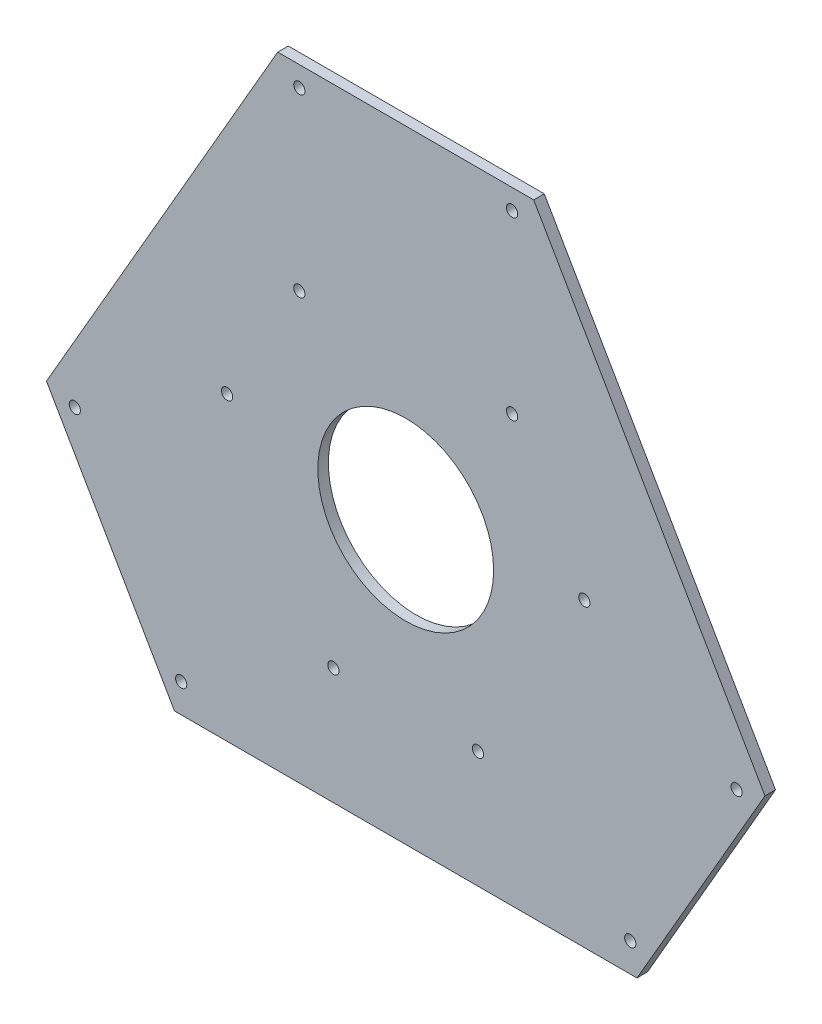
SolidWorks part; units mm, degrees
ref_plane "正面" through (0, 0, 0) normal (0, 0, 1) x (1, 0, 0)
ref_plane "平面" through (0, 0, 0) normal (0, 1, 0) x (1, 0, 0)
ref_plane "右側面" through (0, 0, 0) normal (1, 0, 0) x (0, 0, -1)
sketch "ｽｹｯﾁ1" plane through (0, 0, 0) normal (0, 0, 1) x (1, 0, 0)
  line L0 (0, -55) -> (0, 55) construction
  line L30 (-36.3988, 96.9554) -> (36.3988, 96.9554)
  line L31 (0, 160) -> (-138.5641, -80) construction
  line L32 (-138.5641, -80) -> (138.5641, -80) construction
  line L33 (138.5641, -80) -> (0, 160) construction
  line L34 (36.3988, 96.9554) -> (102.1653, -16.9554)
  line L35 (102.1653, -16.9554) -> (65.7665, -80)
  line L36 (65.7665, -80) -> (-65.7665, -80)
  line L37 (-65.7665, -80) -> (-102.1653, -16.9554)
  line L38 (-102.1653, -16.9554) -> (-36.3988, 96.9554)
  circle A0 centre (30.25, 91.1955) radius 1.6
  circle A1 centre (30.25, 41.1955) radius 1.6
  circle A2 centre (-30.25, 41.1955) radius 1.6
  circle A3 centre (-30.25, 91.1955) radius 1.6
  circle A4 centre (63.8526, -71.795) radius 1.6
  circle A5 centre (94.1026, -19.4005) radius 1.6
  circle A6 centre (50.8013, 5.5995) radius 1.6
  circle A7 centre (20.5513, -46.795) radius 1.6
  circle A8 centre (-94.1026, -19.4005) radius 1.6
  circle A9 centre (-63.8526, -71.795) radius 1.6
  circle A10 centre (-20.5513, -46.795) radius 1.6
  circle A11 centre (-50.8013, 5.5995) radius 1.6
  circle A12 centre (0, 0) radius 80 construction
  circle A17 centre (0, 0) radius 25
  point P0 (0, 60)
  point P1 (0, 0)
  point P2 (0, 0)
  point P46 (0, 0)
  point P48 (0, -80)
  point P76 (0, 0)
  dimension "D1" = 3.2
  dimension "D17" = 50
  dimension "D4" = 50
  dimension "D9" = 80
  dimension "D7" = 3
extrude "ﾎﾞｽ - 押し出し1" add sketch "ｽｹｯﾁ1" along normal blind 3 contours L38 L37 L36 L35 L34 L30 A11 A9 A8 A7 A5 A4 A2 A1 A0 region at (0, 94.2524, 0)
